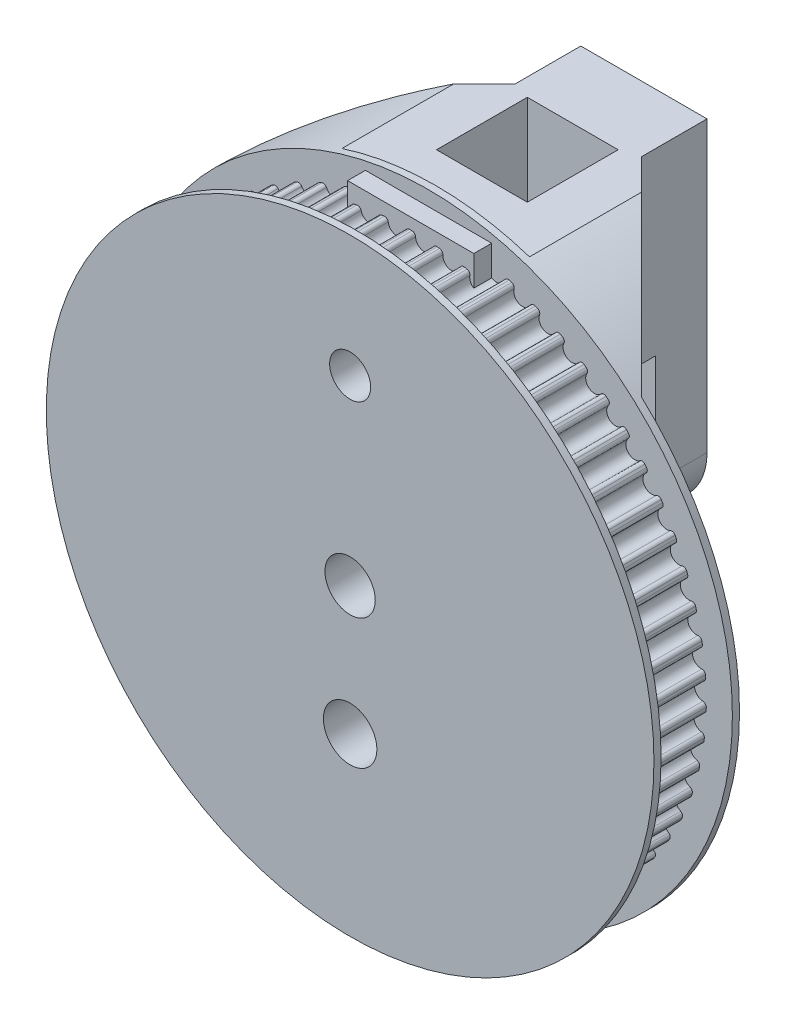
SolidWorks part; units mm, degrees
note: The reader was unsure of these and kept them because the rebuilt part matched: shared geometry of "Sketch1<3>".
other "Markup1"
sketch "Sketch12" plane through (-30, -58, 49.7) normal (-0.8709, -0.4905, 0.0319) x (-0.1533, 0.2093, -0.9658)
other "Markup2"
sketch "Sketch14" plane through (30, -60, 49.7) normal (0.6168, -0.7172, 0.3243) x (-0.4689, -0.0038, 0.8832)
material "PETG"
ref_plane "Front Plane" through (0, 0, 0) normal (0, 0, 1) x (1, 0, 0)
ref_plane "Top Plane" through (0, 0, 0) normal (0, 1, 0) x (1, 0, 0)
ref_plane "Right Plane" through (0, 0, 0) normal (1, 0, 0) x (0, 0, -1)
sketch "Sketch1" plane through (0, 0, 0) normal (0, 1, 0) x (1, 0, 0)
  line L1 (-12.7375, -12.7375) -> (12.7375, -12.7375)
  line L2 (-12.7375, -12.7375) -> (-12.7375, 12.7375)
  line L3 (-12.7375, 12.7375) -> (12.7375, 12.7375)
  line L4 (12.7375, -12.7375) -> (12.7375, 12.7375)
  line L5 (-17.7, -17.7) -> (17.7, -17.7)
  line L6 (-17.7, -17.7) -> (-17.7, 17.7)
  line L7 (-17.7, 17.7) -> (17.7, 17.7)
  line L8 (17.7, -17.7) -> (17.7, 17.7)
  point P8 (0, -17.7)
  point P9 (0, -12.7375)
  point P12 (-17.7, 0)
  point P13 (-12.7375, 0)
  dimension "D1" = 25.475
  dimension "D2" = 35.4
extrude "Boss-Extrude1" add sketch "Sketch1" along normal blind 47.0375
extrude "Boss-Extrude2" add sketch "Sketch1<3>" against normal blind 14.9625 contours L1 L4 L3 L2 | L5 L8 L7 L6 L4 L1 L2 L3
sketch "Sketch1<3>" plane through (0, 0, 0) normal (0, 1, 0) x (1, 0, 0) same geometry as "Sketch1"
sketch "Sketch3" plane through (0, 0, 0) normal (0, -1, 0) x (-1, 0, 0)
  circle A0 centre (0, 0) radius 3.15
  dimension "D1" = 6.3
extrude "Cut-Extrude1" cut sketch "Sketch3" along normal through all
sketch "Sketch13" plane through (0, -14.9625, 0) normal (0, -1, 0) x (1, 0, 0)
  circle A0 centre (0, 0) radius 5.5
  dimension "D1" = 11
extrude "Cut-Extrude4" cut sketch "Sketch13" against normal offset from surface (6.9625 mm away) 8 up to face at (0, 0, -3.15)
sketch "Sketch4" plane through (0, 0, 17.7) normal (0, 0, 1) x (1, 0, 0)
  line L0 (17.7, 47.0375) -> (17.7, -14.9625) construction
  line L1 (-17.7, 47.0375) -> (-17.7, -14.9625) construction
  line L2 (17.7, -34.0125) -> (17.7, -14.9625)
  line L3 (-17.7, -34.0125) -> (-17.7, -14.9625)
  line L5 (17.7, 47.0375) -> (-17.7, 47.0375)
  line L6 (17.7, 47.0375) -> (17.7, -14.9625)
  line L8 (-17.7, 47.0375) -> (-17.7, -14.9625)
  line L9 (-17.7, -14.9625) -> (17.7, -14.9625) construction
  line L10 (-17.7, 47.0375) -> (17.7, 47.0375) construction
  arc A0 (-17.7, -34.0125) -> (17.7, -34.0125) centre (0, -34.0125) ccw
  circle A1 centre (0, -34.0125) radius 7.05
  dimension "D2" = 14.1
  dimension "D1" = 19.05
extrude "Boss-Extrude3" add sketch "Sketch4" along normal blind 15
sketch "Sketch6" plane through (0, 0, 17.7) normal (0, 0, -1) x (-1, 0, 0)
  line L0 (17.7, -34.0125) -> (17.7, -14.9625)
  line L1 (17.7, -14.9625) -> (-17.7, -14.9625)
  line L2 (-17.7, -14.9625) -> (-17.7, -34.0125)
  arc A0 (-17.7, -34.0125) -> (17.7, -34.0125) centre (0, -34.0125) ccw
  arc A4 (-17.7, -34.0125) -> (17.7, -34.0125) centre (0, -34.0125) ccw construction
extrude "Cut-Extrude2" cut sketch "Sketch6" against normal blind 0.5375
sketch "Sketch7" plane through (0, 0, 18.2375) normal (0, 0, -1) x (-1, 0, 0)
  circle A0 centre (0, -34.0125) radius 11.0375
  arc A1 (-17.7, -34.0125) -> (17.7, -34.0125) centre (0, -34.0125) ccw construction
  dimension "D1" = 22.075
extrude "Cut-Extrude3" cut sketch "Sketch7" against normal blind 7
mirror "Mirror1" about plane through (0, 0, 0) normal (0, 0, 1) of "Boss-Extrude3", "Cut-Extrude2", "Cut-Extrude1", "Cut-Extrude3"
sketch "Sketch18" plane through (0, 0, 0) normal (0, 0, 1) x (1, 0, 0)
  line L0 (0, -13.5166) -> (-17.7, -3.2975)
  line L1 (-17.7, -3.2975) -> (-35.45, -34.0414) construction
  line L2 (-35.45, -34.0414) -> (-8.875, -49.3845) construction
  line L3 (-17.7, 47.0375) -> (-17.7, -34.0125) construction
  line L4 (0, -35.0322) -> (0, -50035.0322) construction
  line L5 (-17.7, -3.2975) -> (-17.7, -14.9625)
  line L6 (17.7, -34.0125) -> (17.7, 47.0375) construction
  line L7 (17.7, -3.2975) -> (0, -13.5166)
  line L10 (17.7, -14.9625) -> (17.7, -3.2975)
  line L11 (-17.7, -14.9625) -> (17.7, -14.9625)
  line L12 (-5.5, -14.9625) -> (5.5, -14.9625) construction
  circle A0 centre (0, -34.0125) radius 17.75 construction
  arc A2 (-17.7, -34.0125) -> (17.7, -34.0125) centre (0, -34.0125) ccw construction
  dimension "D2" = 120
  dimension "D1" = 35.5
extrude "Cut-Extrude10" cut sketch "Sketch18" along normal up to surface and the other way up to surface up to face at (-11.0375, -34.0125, 18.2375) other way up to face at (-11.0375, -34.0125, -18.2375)
ref_plane "Plane1" through (0, 0, 27.7) normal (0, 0, 1) x (1, 0, 0)
sketch "Sketch9" plane through (0, 0, 27.7) normal (0, 0, 1) x (1, 0, 0)
  circle A0 centre (0, -34.0125) radius 85.2141
  circle A1 centre (0, -34.0125) radius 7.05 construction
  circle A2 centre (0, -34.0125) radius 7.05
  dimension "D1" = 170.4282
extrude "Boss-Extrude4" add sketch "Sketch9" against normal blind 2
sketch "Sketch10" plane through (0, 0, 27.7) normal (0, 0, -1) x (-1, 0, 0)
  line L0 (0, -41.0625) -> (0, -50041.0625) construction
  line L1 (0, -34.0125) -> (-3.9983, -114.1269) construction
  line L2 (0, -34.0125) -> (3.9983, -114.1269) construction
  circle A0 centre (0, -34.0125) radius 80.2141 construction
  circle A1 centre (0, -34.0125) radius 7.05
  circle A2 centre (0, -34.0125) radius 85.2141 construction
  circle A3 centre (0, -34.0125) radius 7.05 construction
  arc A4 (2.4815, -110.9206) -> (-2.4815, -110.9206) centre (0, -111.1266) ccw
  arc A5 (-3.5233, -111.8369) -> (-2.4815, -110.9206) centre (-3.478, -110.8379) ccw
  circle A6 centre (0, -34.0125) radius 77.9041 construction
  arc A7 (2.4815, -110.9206) -> (3.5233, -111.8369) centre (3.478, -110.8379) ccw
  arc A8 (3.5233, -111.8369) -> (3.8832, -111.8198) centre (0, -34.0125) ccw
  arc A9 (-3.8832, -111.8198) -> (-3.5233, -111.8369) centre (0, -34.0125) ccw
  arc A10 (-11.611, -111.0465) -> (-11.2546, -111.0993) centre (0, -34.0125) ccw
  arc A11 (-11.2546, -111.0993) -> (-10.1267, -110.2914) centre (-11.1101, -110.1098) ccw
  arc A12 (-5.1884, -110.7855) -> (-10.1267, -110.2914) centre (-7.6781, -110.7434) ccw
  arc A13 (-5.1884, -110.7855) -> (-4.243, -111.801) centre (-4.1886, -110.8024) ccw
  arc A14 (-4.243, -111.801) -> (-3.8832, -111.8198) centre (0, -34.0125) ccw
  arc A15 (-19.2234, -109.5076) -> (-18.874, -109.5957) centre (0, -34.0125) ccw
  arc A16 (-18.874, -109.5957) -> (-17.6713, -108.904) centre (-18.6317, -108.6255) ccw
  arc A17 (-12.8068, -109.8874) -> (-17.6713, -108.904) centre (-15.2799, -109.5976) ccw
  arc A18 (-12.8068, -109.8874) -> (-11.9672, -110.9919) centre (-11.8136, -110.0038) ccw
  arc A19 (-11.9672, -110.9919) -> (-11.611, -111.0465) centre (0, -34.0125) ccw
  arc A20 (-26.6448, -107.2184) -> (-26.3059, -107.3409) centre (0, -34.0125) ccw
  arc A21 (-26.3059, -107.3409) -> (-25.0403, -106.7724) centre (-25.9682, -106.3996) ccw
  arc A22 (-20.2978, -108.2352) -> (-25.0403, -106.7724) centre (-22.7298, -107.7006) ccw
  arc A23 (-20.2978, -108.2352) -> (-19.5724, -109.4179) centre (-19.3212, -108.4499) ccw
  arc A24 (-19.5724, -109.4179) -> (-19.2234, -109.5076) centre (0, -34.0125) ccw
  arc A25 (-33.8013, -104.2017) -> (-33.4763, -104.3573) centre (0, -34.0125) ccw
  arc A26 (-33.4763, -104.3573) -> (-32.1604, -103.9176) centre (-33.0466, -103.4543) ccw
  arc A27 (-27.5872, -105.8454) -> (-32.1604, -103.9176) centre (-29.9538, -105.0713) ccw
  arc A28 (-27.5872, -105.8454) -> (-26.9831, -107.0944) centre (-26.6367, -106.1563) ccw
  arc A29 (-26.9831, -107.0944) -> (-26.6448, -107.2184) centre (0, -34.0125) ccw
  arc A30 (-40.6219, -100.4874) -> (-40.314, -100.6745) centre (0, -34.0125) ccw
  arc A31 (-40.314, -100.6745) -> (-38.9609, -100.3681) centre (-39.7965, -99.8188) ccw
  arc A32 (-34.6023, -102.7416) -> (-38.9609, -100.3681) centre (-36.8801, -101.7358) ccw
  arc A33 (-34.6023, -102.7416) -> (-34.1256, -104.0446) centre (-33.6876, -103.1456) ccw
  arc A34 (-34.1256, -104.0446) -> (-33.8013, -104.2017) centre (0, -34.0125) ccw
  arc A35 (-47.0388, -96.1124) -> (-46.7511, -96.3293) centre (0, -34.0125) ccw
  arc A36 (-46.7511, -96.3293) -> (-45.3742, -96.1591) centre (-46.151, -95.5294) ccw
  arc A37 (-41.2736, -98.9548) -> (-45.3742, -96.1591) centre (-43.4399, -97.7272) ccw
  arc A38 (-41.2736, -98.9548) -> (-40.929, -100.2987) centre (-40.4036, -99.4479) ccw
  arc A39 (-40.929, -100.2987) -> (-40.6219, -100.4874) centre (0, -34.0125) ccw
  arc A40 (-52.9882, -91.1202) -> (-52.7235, -91.3647) centre (0, -34.0125) ccw
  arc A41 (-52.7235, -91.3647) -> (-51.3365, -91.3325) centre (-52.0467, -90.6285) ccw
  arc A42 (-47.5347, -94.5226) -> (-51.3365, -91.3325) centre (-49.568, -93.0853) ccw
  arc A43 (-47.5347, -94.5226) -> (-47.3256, -95.8941) centre (-46.7181, -95.0998) ccw
  arc A44 (-47.3256, -95.8941) -> (-47.0388, -96.1124) centre (0, -34.0125) ccw
  arc A45 (-58.411, -85.5605) -> (-58.172, -85.8302) centre (0, -34.0125) ccw
  arc A46 (-58.172, -85.8302) -> (-56.7886, -85.9362) centre (-57.4253, -85.165) ccw
  arc A47 (-53.3233, -89.489) -> (-56.7886, -85.9362) centre (-55.2034, -87.8564) ccw
  arc A48 (-53.3233, -89.489) -> (-53.2518, -90.8745) centre (-52.5683, -90.1446) ccw
  arc A49 (-53.2518, -90.8745) -> (-52.9882, -91.1202) centre (0, -34.0125) ccw
  arc A50 (-63.2533, -79.4885) -> (-63.0423, -79.7806) centre (0, -34.0125) ccw
  arc A51 (-63.0423, -79.7806) -> (-61.6764, -80.0238) centre (-62.233, -79.1931) ccw
  arc A52 (-58.582, -83.904) -> (-61.6764, -80.0238) centre (-60.2902, -82.0923) ccw
  arc A53 (-58.582, -83.904) -> (-58.6488, -85.2898) centre (-57.896, -84.6316) ccw
  arc A54 (-58.6488, -85.2898) -> (-58.411, -85.5605) centre (0, -34.0125) ccw
  arc A55 (-67.4669, -72.9645) -> (-67.286, -73.2762) centre (0, -34.0125) ccw
  arc A56 (-67.286, -73.2762) -> (-65.9511, -73.6542) centre (-66.4223, -72.7722) ccw
  arc A57 (-63.2585, -77.8232) -> (-65.9511, -73.6542) centre (-64.7778, -75.8505) ccw
  arc A58 (-63.2585, -77.8232) -> (-63.463, -79.1955) centre (-62.6483, -78.6155) ccw
  arc A59 (-63.463, -79.1955) -> (-63.2533, -79.4885) centre (0, -34.0125) ccw
  arc A60 (-71.01, -66.0534) -> (-70.8611, -66.3816) centre (0, -34.0125) ccw
  arc A61 (-70.8611, -66.3816) -> (-69.5704, -66.8906) centre (-69.9515, -65.9661) ccw
  arc A62 (-67.3063, -71.307) -> (-69.5704, -66.8906) centre (-68.6217, -69.1928) ccw
  arc A63 (-67.3063, -71.307) -> (-67.6464, -72.6521) centre (-66.778, -72.1561) ccw
  arc A64 (-67.6464, -72.6521) -> (-67.4669, -72.9645) centre (0, -34.0125) ccw
  arc A65 (-73.8474, -58.8239) -> (-73.7319, -59.1652) centre (0, -34.0125) ccw
  arc A66 (-73.7319, -59.1652) -> (-72.4983, -59.8003) centre (-72.7854, -58.8424) ccw
  arc A67 (-70.6852, -64.4201) -> (-72.4983, -59.8003) centre (-71.7835, -62.1854) ccw
  arc A68 (-70.6852, -64.4201) -> (-71.1575, -65.7247) centre (-70.2441, -65.3176) ccw
  arc A69 (-71.1575, -65.7247) -> (-71.01, -66.0534) centre (0, -34.0125) ccw
  arc A70 (-75.9509, -51.3478) -> (-75.8699, -51.6989) centre (0, -34.0125) ccw
  arc A71 (-75.8699, -51.6989) -> (-74.7057, -52.4536) centre (-74.896, -51.4719) ccw
  arc A72 (-73.3615, -57.2311) -> (-74.7057, -52.4536) centre (-74.2319, -54.8981) ccw
  arc A73 (-73.3615, -57.2311) -> (-73.9614, -58.4821) centre (-73.012, -58.168) ccw
  arc A74 (-73.9614, -58.4821) -> (-73.8474, -58.8239) centre (0, -34.0125) ccw
  arc A75 (-77.2995, -43.6994) -> (-77.2539, -44.0568) centre (0, -34.0125) ccw
  arc A76 (-77.2539, -44.0568) -> (-76.1706, -44.9237) centre (-76.2622, -43.9279) ccw
  arc A77 (-75.3088, -49.8112) -> (-76.1706, -44.9237) centre (-75.9426, -47.4032) ccw
  arc A78 (-75.3088, -49.8112) -> (-76.0302, -50.9963) centre (-75.0543, -50.7783) ccw
  arc A79 (-76.0302, -50.9963) -> (-75.9509, -51.3478) centre (0, -34.0125) ccw
  arc A80 (-77.8799, -35.9547) -> (-77.8701, -36.3149) centre (0, -34.0125) ccw
  arc A81 (-77.8701, -36.3149) -> (-76.8785, -37.2853) centre (-76.8705, -36.2854) ccw
  arc A82 (-76.5076, -42.2344) -> (-76.8785, -37.2853) centre (-76.8985, -39.7752) ccw
  arc A83 (-76.5076, -42.2344) -> (-77.3435, -43.3417) centre (-76.3507, -43.222) ccw
  arc A84 (-77.3435, -43.3417) -> (-77.2995, -43.6994) centre (0, -34.0125) ccw
  arc A85 (-77.6863, -28.1907) -> (-77.7124, -28.5501) centre (0, -34.0125) ccw
  arc A86 (-77.7124, -28.5501) -> (-76.8224, -29.6144) centre (-76.7148, -28.6202) ccw
  arc A87 (-76.9461, -34.5758) -> (-76.8224, -29.6144) centre (-77.0901, -32.09) ccw
  arc A88 (-76.9461, -34.5758) -> (-77.888, -35.5945) centre (-76.8882, -35.5741) ccw
  arc A89 (-77.888, -35.5945) -> (-77.8799, -35.9547) centre (0, -34.0125) ccw
  arc A90 (-76.7206, -20.4846) -> (-76.7823, -20.8396) centre (0, -34.0125) ccw
  arc A91 (-76.7823, -20.8396) -> (-76.0027, -21.9873) centre (-75.7967, -21.0087) ccw
  arc A92 (-76.6198, -26.9117) -> (-76.0027, -21.9873) centre (-76.5156, -24.4238) ccw
  arc A93 (-76.6198, -26.9117) -> (-77.6585, -27.8315) centre (-76.6616, -27.9108) ccw
  arc A94 (-77.6585, -27.8315) -> (-77.6863, -28.1907) centre (0, -34.0125) ccw
  arc A95 (-74.9924, -12.9129) -> (-75.0892, -13.26) centre (0, -34.0125) ccw
  arc A96 (-75.0892, -13.26) -> (-74.4277, -14.4796) centre (-74.1253, -13.5264) ccw
  arc A97 (-75.5321, -19.3181) -> (-74.4277, -14.4796) centre (-75.1807, -16.853) ccw
  arc A98 (-75.5321, -19.3181) -> (-76.6572, -20.1299) centre (-75.6732, -20.3081) ccw
  arc A99 (-76.6572, -20.1299) -> (-76.7206, -20.4846) centre (0, -34.0125) ccw
  arc A100 (-72.5189, -5.5509) -> (-72.6497, -5.8867) centre (0, -34.0125) ccw
  arc A101 (-72.6497, -5.8867) -> (-72.113, -7.166) centre (-71.7172, -6.2477) ccw
  arc A102 (-73.6936, -11.8705) -> (-72.113, -7.166) centre (-73.0986, -9.4527) ccw
  arc A103 (-73.6936, -11.8705) -> (-74.894, -12.5663) centre (-73.9326, -12.8416) ccw
  arc A104 (-74.894, -12.5663) -> (-74.9924, -12.9129) centre (0, -34.0125) ccw
  arc A105 (-69.3247, 1.5282) -> (-69.4883, 1.2071) centre (0, -34.0125) ccw
  arc A106 (-69.4883, 1.2071) -> (-69.0816, -0.1193) centre (-68.5963, 0.7551) ccw
  arc A107 (-71.1228, -4.6431) -> (-69.0816, -0.1193) centre (-70.2899, -2.2965) ccw
  arc A108 (-71.1228, -4.6431) -> (-72.3865, -5.2158) centre (-71.4573, -5.5855) ccw
  arc A109 (-72.3865, -5.2158) -> (-72.5189, -5.5509) centre (0, -34.0125) ccw
  arc A110 (-65.4415, 8.2541) -> (-65.6363, 7.9509) centre (0, -34.0125) ccw
  arc A111 (-65.6363, 7.9509) -> (-65.3637, 6.5906) centre (-64.7937, 7.4123) ccw
  arc A112 (-67.8451, 2.2925) -> (-65.3637, 6.5906) centre (-66.7828, 4.5445) ccw
  arc A113 (-67.8451, 2.2925) -> (-69.1595, 1.8485) centre (-68.2718, 1.3881) ccw
  arc A114 (-69.1595, 1.8485) -> (-69.3247, 1.5282) centre (0, -34.0125) ccw
  arc A115 (-60.9079, 14.5599) -> (-61.1319, 14.2777) centre (0, -34.0125) ccw
  arc A116 (-61.1319, 14.2777) -> (-60.9961, 12.8969) centre (-60.3472, 13.6578) ccw
  arc A117 (-63.8932, 8.8673) -> (-60.9961, 12.8969) centre (-62.6119, 11.0024) ccw
  arc A118 (-63.8932, 8.8673) -> (-65.2453, 8.5563) centre (-64.4077, 8.0099) ccw
  arc A119 (-65.2453, 8.5563) -> (-65.4415, 8.2541) centre (0, -34.0125) ccw
  arc A120 (-55.769, 20.383) -> (-56.02, 20.1245) centre (0, -34.0125) ccw
  arc A121 (-56.02, 20.1245) -> (-56.0223, 18.7371) centre (-55.3009, 19.4295) ccw
  arc A122 (-59.3062, 15.016) -> (-56.0223, 18.7371) centre (-57.8187, 17.0128) ccw
  arc A123 (-59.3062, 15.016) -> (-60.6826, 14.8411) centre (-59.9036, 14.214) ccw
  arc A124 (-60.6826, 14.8411) -> (-60.9079, 14.5599) centre (0, -34.0125) ccw
  arc A125 (-50.0758, 25.6655) -> (-50.3513, 25.4332) centre (0, -34.0125) ccw
  arc A126 (-50.3513, 25.4332) -> (-50.4918, 24.053) centre (-49.705, 24.6702) ccw
  arc A127 (-54.1299, 20.6773) -> (-50.4918, 24.053) centre (-52.4509, 22.5161) ccw
  arc A128 (-54.1299, 20.6773) -> (-55.5168, 20.6404) centre (-54.8041, 19.9388) ccw
  arc A129 (-55.5168, 20.6404) -> (-55.769, 20.383) centre (0, -34.0125) ccw
  arc A130 (-43.8849, 30.3549) -> (-44.1822, 30.1512) centre (0, -34.0125) ccw
  arc A131 (-44.1822, 30.1512) -> (-44.4594, 28.7918) centre (-43.6151, 29.3276) ccw
  arc A132 (-48.4155, 25.7951) -> (-44.4594, 28.7918) centre (-46.5618, 27.4576) ccw
  arc A133 (-48.4155, 25.7951) -> (-49.7992, 25.8965) centre (-49.16, 25.1275) ccw
  arc A134 (-49.7992, 25.8965) -> (-50.0758, 25.6655) centre (0, -34.0125) ccw
  arc A135 (-37.2579, 34.4046) -> (-37.574, 34.2315) centre (0, -34.0125) ccw
  arc A136 (-37.574, 34.2315) -> (-37.9852, 32.9064) centre (-37.0917, 33.3555) ccw
  arc A137 (-42.22, 30.3186) -> (-37.9852, 32.9064) centre (-40.21, 31.7883) ccw
  arc A138 (-42.22, 30.3186) -> (-43.5867, 30.5572) centre (-43.0272, 29.7283) ccw
  arc A139 (-43.5867, 30.5572) -> (-43.8849, 30.3549) centre (0, -34.0125) ccw
  arc A140 (-30.2607, 37.7743) -> (-30.5924, 37.6335) centre (0, -34.0125) ccw
  arc A141 (-30.5924, 37.6335) -> (-31.1335, 36.356) centre (-30.1997, 36.7139) ccw
  arc A142 (-35.6049, 34.2027) -> (-31.1335, 36.356) centre (-33.4586, 35.4649) ccw
  arc A143 (-35.6049, 34.2027) -> (-36.9411, 34.5762) centre (-36.4669, 33.6957) ccw
  arc A144 (-36.9411, 34.5762) -> (-37.2579, 34.4046) centre (0, -34.0125) ccw
  arc A145 (-22.9626, 40.4305) -> (-23.3067, 40.3235) centre (0, -34.0125) ccw
  arc A146 (-23.3067, 40.3235) -> (-23.9723, 39.1062) centre (-23.0075, 39.3693) ccw
  arc A147 (-28.6359, 37.4088) -> (-23.9723, 39.1062) centre (-26.3746, 38.451) ccw
  arc A148 (-28.6359, 37.4088) -> (-29.9283, 37.9135) centre (-29.5441, 36.9902) ccw
  arc A149 (-29.9283, 37.9135) -> (-30.2607, 37.7743) centre (0, -34.0125) ccw
  arc A150 (-15.4364, 42.3469) -> (-15.7894, 42.2747) centre (0, -34.0125) ccw
  arc A151 (-15.7894, 42.2747) -> (-16.5729, 41.1297) centre (-15.5867, 41.2955) ccw
  arc A152 (-21.3824, 39.9051) -> (-16.5729, 41.1297) centre (-19.0285, 40.717) ccw
  arc A153 (-21.3824, 39.9051) -> (-22.6181, 40.5359) centre (-22.3277, 39.579) ccw
  arc A154 (-22.6181, 40.5359) -> (-22.9626, 40.4305) centre (0, -34.0125) ccw
  arc A155 (-7.7567, 43.5045) -> (-8.1152, 43.4678) centre (0, -34.0125) ccw
  arc A156 (-8.1152, 43.4678) -> (-9.0088, 42.4065) centre (-8.011, 42.4732) ccw
  arc A157 (-13.9163, 41.6668) -> (-9.0088, 42.4065) centre (-11.4933, 42.2403) ccw
  arc A158 (-13.9163, 41.6668) -> (-15.083, 42.4175) centre (-14.8894, 41.4365) ccw
  arc A159 (-15.083, 42.4175) -> (-15.4364, 42.3469) centre (0, -34.0125) ccw
  arc A160 (0, 43.8916) -> (-0.3603, 43.8908) centre (0, -34.0125) ccw
  arc A161 (-0.3603, 43.8908) -> (-1.3552, 42.9237) centre (-0.3557, 42.8908) ccw
  arc A162 (-6.3119, 42.6763) -> (-1.3552, 42.9237) centre (-3.8438, 43.0057) ccw
  arc A163 (-6.3119, 42.6763) -> (-7.3981, 43.5395) centre (-7.3031, 42.544) ccw
  arc A164 (-7.3981, 43.5395) -> (-7.7567, 43.5045) centre (0, -34.0125) ccw
  arc A165 (7.7567, 43.5045) -> (7.3981, 43.5395) centre (0, -34.0125) ccw
  arc A166 (7.3981, 43.5395) -> (6.3119, 42.6763) centre (7.3031, 42.544) ccw
  arc A167 (1.3552, 42.9237) -> (6.3119, 42.6763) centre (3.8438, 43.0057) ccw
  arc A168 (1.3552, 42.9237) -> (0.3603, 43.8908) centre (0.3557, 42.8908) ccw
  arc A169 (0.3603, 43.8908) -> (0, 43.8916) centre (0, -34.0125) ccw
  arc A170 (15.4364, 42.3469) -> (15.083, 42.4175) centre (0, -34.0125) ccw
  arc A171 (15.083, 42.4175) -> (13.9163, 41.6668) centre (14.8894, 41.4365) ccw
  arc A172 (9.0088, 42.4065) -> (13.9163, 41.6668) centre (11.4933, 42.2403) ccw
  arc A173 (9.0088, 42.4065) -> (8.1152, 43.4678) centre (8.011, 42.4732) ccw
  arc A174 (8.1152, 43.4678) -> (7.7567, 43.5045) centre (0, -34.0125) ccw
  arc A175 (22.9626, 40.4305) -> (22.6181, 40.5359) centre (0, -34.0125) ccw
  arc A176 (22.6181, 40.5359) -> (21.3824, 39.9051) centre (22.3277, 39.579) ccw
  arc A177 (16.5729, 41.1297) -> (21.3824, 39.9051) centre (19.0285, 40.717) ccw
  arc A178 (16.5729, 41.1297) -> (15.7894, 42.2747) centre (15.5867, 41.2955) ccw
  arc A179 (15.7894, 42.2747) -> (15.4364, 42.3469) centre (0, -34.0125) ccw
  arc A180 (30.2607, 37.7743) -> (29.9283, 37.9135) centre (0, -34.0125) ccw
  arc A181 (29.9283, 37.9135) -> (28.6359, 37.4088) centre (29.5441, 36.9902) ccw
  arc A182 (23.9723, 39.1062) -> (28.6359, 37.4088) centre (26.3746, 38.451) ccw
  arc A183 (23.9723, 39.1062) -> (23.3067, 40.3235) centre (23.0075, 39.3693) ccw
  arc A184 (23.3067, 40.3235) -> (22.9626, 40.4305) centre (0, -34.0125) ccw
  arc A185 (37.2579, 34.4046) -> (36.9411, 34.5762) centre (0, -34.0125) ccw
  arc A186 (36.9411, 34.5762) -> (35.6049, 34.2027) centre (36.4669, 33.6957) ccw
  arc A187 (31.1335, 36.356) -> (35.6049, 34.2027) centre (33.4586, 35.4649) ccw
  arc A188 (31.1335, 36.356) -> (30.5924, 37.6335) centre (30.1997, 36.7139) ccw
  arc A189 (30.5924, 37.6335) -> (30.2607, 37.7743) centre (0, -34.0125) ccw
  arc A190 (43.8849, 30.3549) -> (43.5867, 30.5572) centre (0, -34.0125) ccw
  arc A191 (43.5867, 30.5572) -> (42.22, 30.3186) centre (43.0272, 29.7283) ccw
  arc A192 (37.9852, 32.9064) -> (42.22, 30.3186) centre (40.21, 31.7883) ccw
  arc A193 (37.9852, 32.9064) -> (37.574, 34.2315) centre (37.0917, 33.3555) ccw
  arc A194 (37.574, 34.2315) -> (37.2579, 34.4046) centre (0, -34.0125) ccw
  arc A195 (50.0758, 25.6655) -> (49.7992, 25.8965) centre (0, -34.0125) ccw
  arc A196 (49.7992, 25.8965) -> (48.4155, 25.7951) centre (49.16, 25.1275) ccw
  arc A197 (44.4594, 28.7918) -> (48.4155, 25.7951) centre (46.5618, 27.4576) ccw
  arc A198 (44.4594, 28.7918) -> (44.1822, 30.1512) centre (43.6151, 29.3276) ccw
  arc A199 (44.1822, 30.1512) -> (43.8849, 30.3549) centre (0, -34.0125) ccw
  arc A200 (55.769, 20.383) -> (55.5168, 20.6404) centre (0, -34.0125) ccw
  arc A201 (55.5168, 20.6404) -> (54.1299, 20.6773) centre (54.8041, 19.9388) ccw
  arc A202 (50.4918, 24.053) -> (54.1299, 20.6773) centre (52.4509, 22.5161) ccw
  arc A203 (50.4918, 24.053) -> (50.3513, 25.4332) centre (49.705, 24.6702) ccw
  arc A204 (50.3513, 25.4332) -> (50.0758, 25.6655) centre (0, -34.0125) ccw
  arc A205 (60.9079, 14.5599) -> (60.6826, 14.8411) centre (0, -34.0125) ccw
  arc A206 (60.6826, 14.8411) -> (59.3062, 15.016) centre (59.9036, 14.214) ccw
  arc A207 (56.0223, 18.7371) -> (59.3062, 15.016) centre (57.8187, 17.0128) ccw
  arc A208 (56.0223, 18.7371) -> (56.02, 20.1245) centre (55.3009, 19.4295) ccw
  arc A209 (56.02, 20.1245) -> (55.769, 20.383) centre (0, -34.0125) ccw
  arc A210 (65.4415, 8.2541) -> (65.2453, 8.5563) centre (0, -34.0125) ccw
  arc A211 (65.2453, 8.5563) -> (63.8932, 8.8673) centre (64.4077, 8.0099) ccw
  arc A212 (60.9961, 12.8969) -> (63.8932, 8.8673) centre (62.6119, 11.0024) ccw
  arc A213 (60.9961, 12.8969) -> (61.1319, 14.2777) centre (60.3472, 13.6578) ccw
  arc A214 (61.1319, 14.2777) -> (60.9079, 14.5599) centre (0, -34.0125) ccw
  arc A215 (69.3247, 1.5282) -> (69.1595, 1.8485) centre (0, -34.0125) ccw
  arc A216 (69.1595, 1.8485) -> (67.8451, 2.2925) centre (68.2718, 1.3881) ccw
  arc A217 (65.3637, 6.5906) -> (67.8451, 2.2925) centre (66.7828, 4.5445) ccw
  arc A218 (65.3637, 6.5906) -> (65.6363, 7.9509) centre (64.7937, 7.4123) ccw
  arc A219 (65.6363, 7.9509) -> (65.4415, 8.2541) centre (0, -34.0125) ccw
  arc A220 (72.5189, -5.5509) -> (72.3865, -5.2158) centre (0, -34.0125) ccw
  arc A221 (72.3865, -5.2158) -> (71.1228, -4.6431) centre (71.4573, -5.5855) ccw
  arc A222 (69.0816, -0.1193) -> (71.1228, -4.6431) centre (70.2899, -2.2965) ccw
  arc A223 (69.0816, -0.1193) -> (69.4883, 1.2071) centre (68.5963, 0.7551) ccw
  arc A224 (69.4883, 1.2071) -> (69.3247, 1.5282) centre (0, -34.0125) ccw
  arc A225 (74.9924, -12.9129) -> (74.894, -12.5663) centre (0, -34.0125) ccw
  arc A226 (74.894, -12.5663) -> (73.6936, -11.8705) centre (73.9326, -12.8416) ccw
  arc A227 (72.113, -7.166) -> (73.6936, -11.8705) centre (73.0986, -9.4527) ccw
  arc A228 (72.113, -7.166) -> (72.6497, -5.8867) centre (71.7172, -6.2477) ccw
  arc A229 (72.6497, -5.8867) -> (72.5189, -5.5509) centre (0, -34.0125) ccw
  arc A230 (76.7206, -20.4846) -> (76.6572, -20.1299) centre (0, -34.0125) ccw
  arc A231 (76.6572, -20.1299) -> (75.5321, -19.3181) centre (75.6732, -20.3081) ccw
  arc A232 (74.4277, -14.4796) -> (75.5321, -19.3181) centre (75.1807, -16.853) ccw
  arc A233 (74.4277, -14.4796) -> (75.0892, -13.26) centre (74.1253, -13.5264) ccw
  arc A234 (75.0892, -13.26) -> (74.9924, -12.9129) centre (0, -34.0125) ccw
  arc A235 (77.6863, -28.1907) -> (77.6585, -27.8315) centre (0, -34.0125) ccw
  arc A236 (77.6585, -27.8315) -> (76.6198, -26.9117) centre (76.6616, -27.9108) ccw
  arc A237 (76.0027, -21.9873) -> (76.6198, -26.9117) centre (76.5156, -24.4238) ccw
  arc A238 (76.0027, -21.9873) -> (76.7823, -20.8396) centre (75.7967, -21.0087) ccw
  arc A239 (76.7823, -20.8396) -> (76.7206, -20.4846) centre (0, -34.0125) ccw
  arc A240 (77.8799, -35.9547) -> (77.888, -35.5945) centre (0, -34.0125) ccw
  arc A241 (77.888, -35.5945) -> (76.9461, -34.5758) centre (76.8882, -35.5741) ccw
  arc A242 (76.8224, -29.6144) -> (76.9461, -34.5758) centre (77.0901, -32.09) ccw
  arc A243 (76.8224, -29.6144) -> (77.7124, -28.5501) centre (76.7148, -28.6202) ccw
  arc A244 (77.7124, -28.5501) -> (77.6863, -28.1907) centre (0, -34.0125) ccw
  arc A245 (77.2995, -43.6994) -> (77.3435, -43.3417) centre (0, -34.0125) ccw
  arc A246 (77.3435, -43.3417) -> (76.5076, -42.2344) centre (76.3507, -43.222) ccw
  arc A247 (76.8785, -37.2853) -> (76.5076, -42.2344) centre (76.8985, -39.7752) ccw
  arc A248 (76.8785, -37.2853) -> (77.8701, -36.3149) centre (76.8705, -36.2854) ccw
  arc A249 (77.8701, -36.3149) -> (77.8799, -35.9547) centre (0, -34.0125) ccw
  arc A250 (75.9509, -51.3478) -> (76.0302, -50.9963) centre (0, -34.0125) ccw
  arc A251 (76.0302, -50.9963) -> (75.3088, -49.8112) centre (75.0543, -50.7783) ccw
  arc A252 (76.1706, -44.9237) -> (75.3088, -49.8112) centre (75.9426, -47.4032) ccw
  arc A253 (76.1706, -44.9237) -> (77.2539, -44.0568) centre (76.2622, -43.9279) ccw
  arc A254 (77.2539, -44.0568) -> (77.2995, -43.6994) centre (0, -34.0125) ccw
  arc A255 (73.8474, -58.8239) -> (73.9614, -58.4821) centre (0, -34.0125) ccw
  arc A256 (73.9614, -58.4821) -> (73.3615, -57.2311) centre (73.012, -58.168) ccw
  arc A257 (74.7057, -52.4536) -> (73.3615, -57.2311) centre (74.2319, -54.8981) ccw
  arc A258 (74.7057, -52.4536) -> (75.8699, -51.6989) centre (74.896, -51.4719) ccw
  arc A259 (75.8699, -51.6989) -> (75.9509, -51.3478) centre (0, -34.0125) ccw
  arc A260 (71.01, -66.0534) -> (71.1575, -65.7247) centre (0, -34.0125) ccw
  arc A261 (71.1575, -65.7247) -> (70.6852, -64.4201) centre (70.2441, -65.3176) ccw
  arc A262 (72.4983, -59.8003) -> (70.6852, -64.4201) centre (71.7835, -62.1854) ccw
  arc A263 (72.4983, -59.8003) -> (73.7319, -59.1652) centre (72.7854, -58.8424) ccw
  arc A264 (73.7319, -59.1652) -> (73.8474, -58.8239) centre (0, -34.0125) ccw
  arc A265 (67.4669, -72.9645) -> (67.6464, -72.6521) centre (0, -34.0125) ccw
  arc A266 (67.6464, -72.6521) -> (67.3063, -71.307) centre (66.778, -72.1561) ccw
  arc A267 (69.5704, -66.8906) -> (67.3063, -71.307) centre (68.6217, -69.1928) ccw
  arc A268 (69.5704, -66.8906) -> (70.8611, -66.3816) centre (69.9515, -65.9661) ccw
  arc A269 (70.8611, -66.3816) -> (71.01, -66.0534) centre (0, -34.0125) ccw
  arc A270 (63.2533, -79.4885) -> (63.463, -79.1955) centre (0, -34.0125) ccw
  arc A271 (63.463, -79.1955) -> (63.2585, -77.8232) centre (62.6483, -78.6155) ccw
  arc A272 (65.9511, -73.6542) -> (63.2585, -77.8232) centre (64.7778, -75.8505) ccw
  arc A273 (65.9511, -73.6542) -> (67.286, -73.2762) centre (66.4223, -72.7722) ccw
  arc A274 (67.286, -73.2762) -> (67.4669, -72.9645) centre (0, -34.0125) ccw
  arc A275 (58.411, -85.5605) -> (58.6488, -85.2898) centre (0, -34.0125) ccw
  arc A276 (58.6488, -85.2898) -> (58.582, -83.904) centre (57.896, -84.6316) ccw
  arc A277 (61.6764, -80.0238) -> (58.582, -83.904) centre (60.2902, -82.0923) ccw
  arc A278 (61.6764, -80.0238) -> (63.0423, -79.7806) centre (62.233, -79.1931) ccw
  arc A279 (63.0423, -79.7806) -> (63.2533, -79.4885) centre (0, -34.0125) ccw
  arc A280 (52.9882, -91.1202) -> (53.2518, -90.8745) centre (0, -34.0125) ccw
  arc A281 (53.2518, -90.8745) -> (53.3233, -89.489) centre (52.5683, -90.1446) ccw
  arc A282 (56.7886, -85.9362) -> (53.3233, -89.489) centre (55.2034, -87.8564) ccw
  arc A283 (56.7886, -85.9362) -> (58.172, -85.8302) centre (57.4253, -85.165) ccw
  arc A284 (58.172, -85.8302) -> (58.411, -85.5605) centre (0, -34.0125) ccw
  arc A285 (47.0388, -96.1124) -> (47.3256, -95.8941) centre (0, -34.0125) ccw
  arc A286 (47.3256, -95.8941) -> (47.5347, -94.5226) centre (46.7181, -95.0998) ccw
  arc A287 (51.3365, -91.3325) -> (47.5347, -94.5226) centre (49.568, -93.0853) ccw
  arc A288 (51.3365, -91.3325) -> (52.7235, -91.3647) centre (52.0467, -90.6285) ccw
  arc A289 (52.7235, -91.3647) -> (52.9882, -91.1202) centre (0, -34.0125) ccw
  arc A290 (40.6219, -100.4874) -> (40.929, -100.2987) centre (0, -34.0125) ccw
  arc A291 (40.929, -100.2987) -> (41.2736, -98.9548) centre (40.4036, -99.4479) ccw
  arc A292 (45.3742, -96.1591) -> (41.2736, -98.9548) centre (43.4399, -97.7272) ccw
  arc A293 (45.3742, -96.1591) -> (46.7511, -96.3293) centre (46.151, -95.5294) ccw
  arc A294 (46.7511, -96.3293) -> (47.0388, -96.1124) centre (0, -34.0125) ccw
  arc A295 (33.8013, -104.2017) -> (34.1256, -104.0446) centre (0, -34.0125) ccw
  arc A296 (34.1256, -104.0446) -> (34.6023, -102.7416) centre (33.6876, -103.1456) ccw
  arc A297 (38.9609, -100.3681) -> (34.6023, -102.7416) centre (36.8801, -101.7358) ccw
  arc A298 (38.9609, -100.3681) -> (40.314, -100.6745) centre (39.7965, -99.8188) ccw
  arc A299 (40.314, -100.6745) -> (40.6219, -100.4874) centre (0, -34.0125) ccw
  arc A300 (26.6448, -107.2184) -> (26.9831, -107.0944) centre (0, -34.0125) ccw
  arc A301 (26.9831, -107.0944) -> (27.5872, -105.8454) centre (26.6367, -106.1563) ccw
  arc A302 (32.1604, -103.9176) -> (27.5872, -105.8454) centre (29.9538, -105.0713) ccw
  arc A303 (32.1604, -103.9176) -> (33.4763, -104.3573) centre (33.0466, -103.4543) ccw
  arc A304 (33.4763, -104.3573) -> (33.8013, -104.2017) centre (0, -34.0125) ccw
  arc A305 (19.2234, -109.5076) -> (19.5724, -109.4179) centre (0, -34.0125) ccw
  arc A306 (19.5724, -109.4179) -> (20.2978, -108.2352) centre (19.3212, -108.4499) ccw
  arc A307 (25.0403, -106.7724) -> (20.2978, -108.2352) centre (22.7298, -107.7006) ccw
  arc A308 (25.0403, -106.7724) -> (26.3059, -107.3409) centre (25.9682, -106.3996) ccw
  arc A309 (26.3059, -107.3409) -> (26.6448, -107.2184) centre (0, -34.0125) ccw
  arc A310 (11.611, -111.0465) -> (11.9672, -110.9919) centre (0, -34.0125) ccw
  arc A311 (11.9672, -110.9919) -> (12.8068, -109.8874) centre (11.8136, -110.0038) ccw
  arc A312 (17.6713, -108.904) -> (12.8068, -109.8874) centre (15.2799, -109.5976) ccw
  arc A313 (17.6713, -108.904) -> (18.874, -109.5957) centre (18.6317, -108.6255) ccw
  arc A314 (18.874, -109.5957) -> (19.2234, -109.5076) centre (0, -34.0125) ccw
  arc A315 (3.8832, -111.8198) -> (4.243, -111.801) centre (0, -34.0125) ccw
  arc A316 (4.243, -111.801) -> (5.1884, -110.7855) centre (4.1886, -110.8024) ccw
  arc A317 (10.1267, -110.2914) -> (5.1884, -110.7855) centre (7.6781, -110.7434) ccw
  arc A318 (10.1267, -110.2914) -> (11.2546, -111.0993) centre (11.1101, -110.1098) ccw
  arc A319 (11.2546, -111.0993) -> (11.611, -111.0465) centre (0, -34.0125) ccw
  point P10 (0, -108.6366)
  point P14 (0, -111.9166)
  point P27 (0, -114.2266)
  dimension "D1" = 160.4282
  dimension "D2" = 2.49
  dimension "D3" = 1
  dimension "D4" = 3.28
  dimension "D6" = 5.59
  dimension "D5" = 8
  dimension "D7" = 63
extrude "Boss-Extrude5" add sketch "Sketch10" against normal blind 20
sketch "Sketch11" plane through (0, 0, 47.7) normal (0, 0, 1) x (1, 0, 0)
  circle A0 centre (0, -34.0125) radius 85.2141
  circle A1 centre (0, -34.0125) radius 7.05
  circle A3 centre (0, -34.0125) radius 85.2141 construction
  circle A4 centre (0, -34.0125) radius 7.05 construction
extrude "Boss-Extrude6" add sketch "Sketch11" along normal blind 2
sketch "Sketch15" plane through (0, 0, -32.7) normal (0, 0, -1) x (-1, 0, 0)
  line L1 (0, 17.0375) -> (-17.7, 17.0375) construction
  line L2 (0, 17.0375) -> (17.7, 17.0375) construction
  line L3 (17.7, 47.0375) -> (17.7, -34.0125) construction
  line L4 (-17.7, -34.0125) -> (-17.7, 47.0375) construction
  line L5 (-17.7, 47.0375) -> (17.7, 47.0375) construction
  circle A0 centre (0, 17.0375) radius 3.25
  dimension "D1" = 6.5
  dimension "D2" = 30
extrude "Cut-Extrude5" cut sketch "Sketch15" against normal up to next
sketch "Sketch16" plane through (0, 0, -32.7) normal (0, 0, -1) x (-1, 0, 0)
  circle A0 centre (0, 17.0375) radius 5.75
  circle A1 centre (0, 17.0375) radius 3.25 construction
  dimension "D1" = 11.5
extrude "Cut-Extrude6" cut sketch "Sketch16" against normal blind 10 and the other way through all
mirror "Mirror2" about plane through (0, 0, 0) normal (0, 0, 1) of "Cut-Extrude5", "Cut-Extrude6"
sketch "Sketch17" plane through (0, 0, 25.7) normal (0, 0, -1) x (-1, 0, 0)
  line L0 (8.875, -49.3845) -> (81.0538, -7.712) construction
  line L1 (81.0538, -7.712) -> (63.3038, 23.0319) construction
  line L2 (63.3038, 23.0319) -> (-8.875, -18.6405) construction
  line L3 (0, -31.0125) -> (0, -50031.0125) construction
  line L4 (17.7, -3.2975) -> (17.7, 47.0375)
  line L5 (17.7, 47.0375) -> (17.7, -34.0125) construction
  line L6 (17.7, 47.0375) -> (17.7, -34.0125) construction
  line L8 (57.7, 28.6944) -> (57.7, 19.7965)
  line L9 (57.7, 19.7965) -> (17.7, -3.2975)
  line L10 (17.7, 47.0375) -> (26.3123, 47.0375)
  circle A0 centre (0, -34.0125) radius 17.75 construction
  circle A1 centre (0, -34.0125) radius 85.2141 construction
  arc A3 (57.7, 28.6944) -> (26.3123, 47.0375) centre (0, -34.0125) ccw
  dimension "D2" = 120
  dimension "D3" = 40
  dimension "D1" = 35.5
extrude "Boss-Extrude7" add sketch "Sketch17" along normal blind 40
chamfer "Chamfer1" distance 40 angle 45 1 edges at (-57.7, 24.2455, -14.3)
mirror "Mirror3" about plane through (0, 0, 0) normal (1, 0, 0) of "Chamfer1", "Boss-Extrude7"
sketch "Sketch19" plane through (0, 0, 49.7) normal (0, 0, 1) x (1, 0, 0)
  circle A0 centre (0, -70.0125) radius 7.5
  circle A1 centre (0, -34.0125) radius 7.05 construction
  dimension "D1" = 36
  dimension "D2" = 15
extrude "Cut-Extrude11" cut sketch "Sketch19" against normal through all
equation "\"tol_dia_id_intfc\" = 0.0500mm ' For hole diameters - Interference fit"
equation "\"tol_dia_id_slip\"  = 0.0750mm ' For hole diameters - Slip fit"
equation "\"tol_dia_id_clear\" = 0.1000mm ' For hole diameters - Clearance fit"
equation "\"tol_dia_od_intfc\" = 0.0500mm ' For shaft diameters - Interference fit"
equation "\"tol_dia_od_slip\"  = 0.0750mm ' For shaft diameters - Slip fit"
equation "\"tol_dia_od_clear\" = 0.1000mm ' For shaft diameters - Clearance fit"
equation "\"tol_general_intfc\"= 0.0250mm ' For general parts (Horiz) - Interference fit"
equation "\"tol_general_slip\" = 0.0375mm ' For general parts (Horiz) - Slip fit"
equation "\"tol_general_clear\"= 0.0500mm ' For general parts (Horiz) - Clearance fit"
equation "\"tol_layer_intfc\"  = 0.0250mm ' For all parts (Vert) - Interference fit"
equation "\"tol_layer_slip\"   = 0.0375mm ' For all parts (Vert) - Slip fit"
equation "\"tol_layer_clear\"  = 0.0500mm ' For all parts (Vert) - Clearance fit"
equation "\"tol_corner_rad\"   = 0.100mm ' For corners that fit into other parts"
equation "\"pitch\"= 8mm"
equation "\"n\"=63"
equation "\"pitch_dia\"= \"pitch\" * \"n\" / PI"
equation "\"belt_width\"= 20mm"
equation "\"pulley_chamfer\"= 40mm"
equation "\"D1@Sketch1\"= 25.4 + \"tol_general_slip\" * 2"
equation "\"D2@Sketch1\"=25.4+10"
equation "\"D1@Boss-Extrude1\"=47.00mm+\"tol_layer_slip\""
equation "\"D1@Boss-Extrude2\"=15.00mm-\"tol_layer_slip\""
equation "\"D2@Sketch4\"= 14.00mm + \"tol_dia_id_clear\""
equation "\"D1@Sketch4\"= 19.00mm + \"tol_layer_clear\""
equation "\"D1@Sketch7\"= 22.00mm + \"tol_dia_id_slip\""
equation "\"D1@Cut-Extrude2\"=0.50mm+\"tol_general_slip\""
equation "\"D1@Boss-Extrude5\"=\"belt_width\""
equation "\"D1@Sketch10\"=\"pitch_dia\""
equation "\"D1@Sketch9\"=\"pitch_dia\"+10.00mm"
equation "\"D1@Boss-Extrude7\"=\"pulley_chamfer\""
equation "\"D1@Chamfer1\"=\"pulley_chamfer\""
equation "\"D3@Sketch17\"=\"pulley_chamfer\""
equation "\"D1@Sketch17\"=35.40mm+\"tol_general_clear\"*2"
equation "\"D1@Sketch18\"=35.40+\"tol_general_clear\"*2"
equation "\"D7@Sketch10\"=\"n\""
equation "\"D5@Sketch10\"=\"pitch\""
